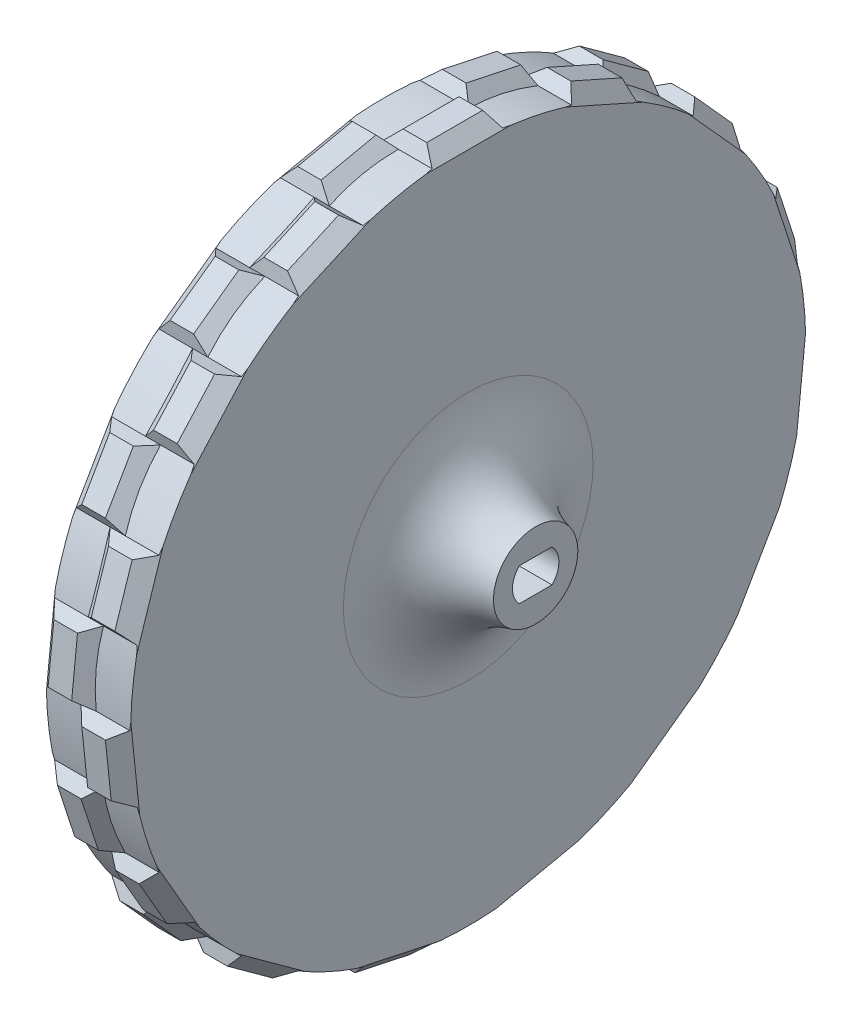
SolidWorks part; units mm, degrees
ref_plane "Front Plane" through (0, 0, 0) normal (0, 0, 1) x (1, 0, 0)
ref_plane "Top Plane" through (0, 0, 0) normal (0, 1, 0) x (1, 0, 0)
ref_plane "Right Plane" through (0, 0, 0) normal (1, 0, 0) x (0, 0, -1)
sketch "Sketch1" plane through (0, 0, 0) normal (1, 0, 0) x (0, 0, -1)
  circle A0 centre (0, 0) radius 40
  dimension "D1" = 80
extrude "Boss-Extrude1" add sketch "Sketch1" along normal blind 10
sketch "Sketch2" plane through (10, 0, 0) normal (1, 0, 0) x (0, 0, -1)
  line L0 (-4.1811, 39.7809) -> (-3.3151, 41.2809)
  line L1 (-3.3151, 41.2809) -> (3.3151, 41.2809)
  line L2 (3.3151, 41.2809) -> (4.1811, 39.7809)
  line L3 (4.1811, 39.7809) -> (-4.1811, 39.7809)
  line L4 (-4.1811, 39.7809) -> (0, 0) construction
  line L5 (0, 0) -> (4.1811, 39.7809) construction
  circle A0 centre (0, 0) radius 40 construction
  point P4 (0, 39.7809)
  dimension "D1" = 60
  dimension "D2" = 60
  dimension "D4" = 1.5
  dimension "D3" = 12
extrude "Boss-Extrude2" add sketch "Sketch2" against normal blind 6
chamfer "Chamfer1" distance 1.6 angle 45 2 edges at (10, 41.2809, 0) (4, 41.2809, 0)
pattern_circular "CirPattern1" count 15 over 360 about axis through (10, 0, 0) along (1, 0, 0) of "Boss-Extrude2", "Chamfer1"
sketch "Sketch4" plane through (0, 0, 0) normal (-1, 0, 0) x (0, 0, 1)
  line L0 (0, 40) -> (0, 0) construction
  line L1 (0, 0) -> (-8.3165, 39.1259) construction
  line L6 (-12.3607, 38.0423) -> (-4.1811, 39.7809)
  line L7 (-4.1811, 39.7809) -> (-5.3401, 41.068)
  line L8 (-5.3401, 41.068) -> (-11.8254, 39.6895)
  line L9 (-11.8254, 39.6895) -> (-12.3607, 38.0423)
  line L10 (-12.3607, 38.0423) -> (0, 0) construction
  line L11 (0, 0) -> (-4.1811, 39.7809) construction
  circle A1 centre (0, 0) radius 40 construction
  point P13 (-8.2709, 38.9116)
  dimension "D2" = 60
  dimension "D1" = 12
  dimension "D3" = 60
  dimension "D4" = 12
  dimension "D5" = 1.5
extrude "Boss-Extrude3" add sketch "Sketch4" against normal blind 6
chamfer "Chamfer2" distance 1.6 angle 45 2 edges at (6, 40.3788, -8.5828) (0, 40.3788, -8.5828)
pattern_circular "CirPattern2" count 15 over 360 about axis through (0, 0, 0) along (1, 0, 0) of "Boss-Extrude3", "Chamfer2"
sketch "Sketch5" plane through (10, 0, 0) normal (1, 0, 0) x (0, 0, -1)
  circle A0 centre (0, 0) radius 5
  dimension "D1" = 10
extrude "Boss-Extrude4" add sketch "Sketch5" along normal blind 8
sketch "Sketch6" plane through (18, 0, 0) normal (1, 0, 0) x (0, 0, -1)
  line L0 (-1.9391, 1.95) -> (1.9391, 1.95)
  line L1 (1.9391, -1.95) -> (-1.9391, -1.95)
  circle A0 centre (0, 0) radius 2.75
  dimension "D1" = 5.5
  dimension "D2" = 3.9
extrude "Cut-Extrude1" cut sketch "Sketch6" against normal blind 8 contours L0 A0 L1 region at (18, 0, 0)
fillet "Fillet1" radius 10 1 edges at (10, 0, -5)
equation "\"D2@Sketch2\"=\"D1@Sketch2\""
equation "\"D3@Sketch4\"=\"D2@Sketch4\""
equation "\"Num Treads\"= 15"
equation "\"D1@CirPattern1\"=\"Num Treads\""
equation "\"D1@CirPattern2\"=\"Num Treads\""
